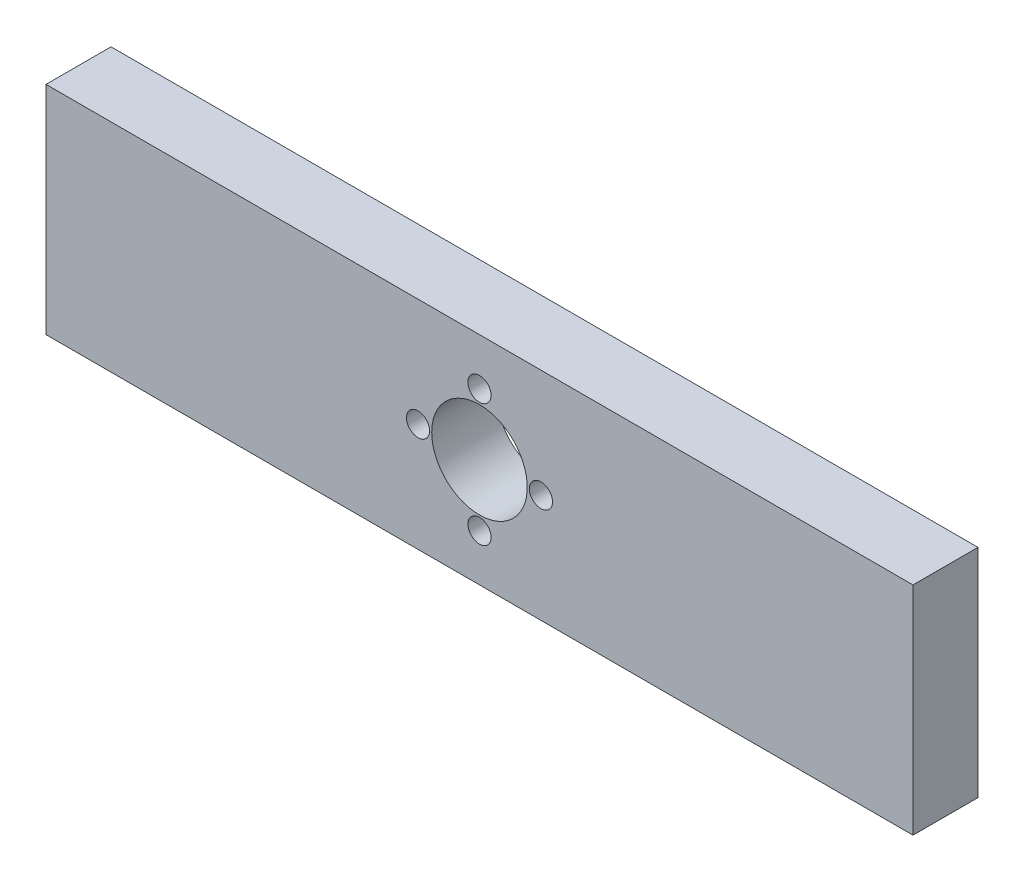
SolidWorks part; units mm, degrees
material "PE High Density Film"
ref_plane "Front Plane" through (0, 0, 0) normal (0, 0, 1) x (1, 0, 0)
ref_plane "Top Plane" through (0, 0, 0) normal (0, 1, 0) x (1, 0, 0)
ref_plane "Right Plane" through (0, 0, 0) normal (1, 0, 0) x (0, 0, -1)
sketch "Sketch1" plane through (0, 0, 0) normal (0, 0, 1) x (1, 0, 0)
  line L0 (-1.1838, 11.4734) -> (-11.4734, 1.1838) construction
  line L1 (-63.5, 15.875) -> (63.5, 15.875)
  line L2 (-63.5, 15.875) -> (-63.5, -15.875)
  line L3 (-63.5, -15.875) -> (63.5, -15.875)
  line L4 (63.5, 15.875) -> (63.5, -15.875)
  line L5 (-63.5, 15.875) -> (63.5, -15.875) construction
  line L6 (-63.5, -15.875) -> (63.5, 15.875) construction
  line L7 (-11.4734, -1.1838) -> (-1.1838, -11.4734) construction
  line L8 (1.1838, -11.4734) -> (11.4734, -1.1838) construction
  line L9 (11.4734, 1.1838) -> (1.1838, 11.4734) construction
  circle A0 centre (0, -9) radius 1.7
  circle A1 centre (-9, 0) radius 1.7
  circle A2 centre (0, 9) radius 1.7
  circle A3 centre (9, 0) radius 1.7
  arc A4 (-11.4734, 1.1838) -> (-11.677, 0.7327) centre (-10.9784, 0.6889) ccw construction
  arc A5 (-11.677, 0.7327) -> (-11.677, -0.7327) centre (0, 0) ccw construction
  arc A6 (-11.677, -0.7327) -> (-11.4734, -1.1838) centre (-10.9784, -0.6889) ccw construction
  arc A7 (-1.1838, -11.4734) -> (-0.7327, -11.677) centre (-0.6889, -10.9784) ccw construction
  arc A8 (-0.7327, -11.677) -> (0.7327, -11.677) centre (0, 0) ccw construction
  arc A9 (0.7327, -11.677) -> (1.1838, -11.4734) centre (0.6889, -10.9784) ccw construction
  arc A10 (11.4734, -1.1838) -> (11.677, -0.7327) centre (10.9784, -0.6889) ccw construction
  arc A11 (11.677, -0.7327) -> (11.677, 0.7327) centre (0, 0) ccw construction
  arc A12 (11.677, 0.7327) -> (11.4734, 1.1838) centre (10.9784, 0.6889) ccw construction
  arc A13 (1.1838, 11.4734) -> (0.7327, 11.677) centre (0.6889, 10.9784) ccw construction
  arc A14 (0.7327, 11.677) -> (-0.7327, 11.677) centre (0, 0) ccw construction
  arc A15 (-0.7327, 11.677) -> (-1.1838, 11.4734) centre (-0.6889, 10.9784) ccw construction
  circle A16 centre (0, 0) radius 7
  point P0 (0, 0)
  dimension "D3" = 3.4
  dimension "D6" = 14
  dimension "D1" = 127
  dimension "D2" = 31.75
  dimension "D4" = 14.5516
  dimension "D5" = 90
extrude "Boss-Extrude1" add sketch "Sketch1" along normal blind 9.525
